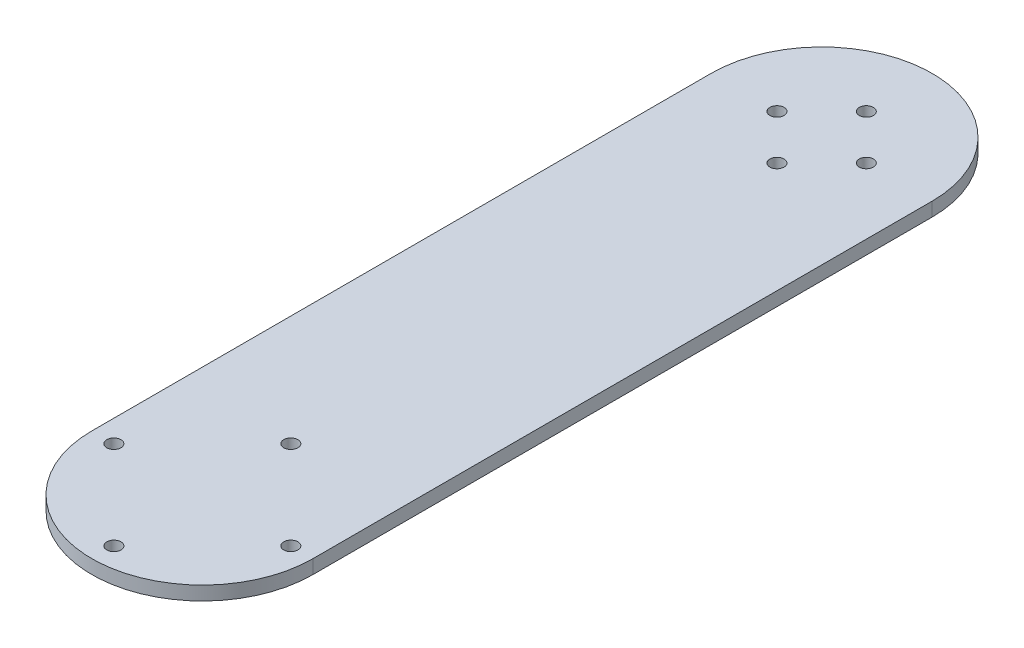
SolidWorks part; units mm, degrees
note: The reader was unsure of these and kept them because the rebuilt part matched: thickness of "Base-Flange1", "Sheet-Metal1", "Sheet-Metal2", "Sheet-Metal4".
ref_plane "Front Plane" through (0, 0, 0) normal (0, 0, 1) x (1, 0, 0)
ref_plane "Top Plane" through (0, 0, 0) normal (0, 1, 0) x (1, 0, 0)
ref_plane "Right Plane" through (0, 0, 0) normal (1, 0, 0) x (0, 0, -1)
sketch "Sketch1" plane through (0, 0, 0) normal (0, 1, 0) x (1, 0, 0)
  line L0 (0, 0) -> (0, -140) construction
  line L2 (-25, 0) -> (-25, -140)
  line L4 (25, 0) -> (25, -140)
  arc A0 (25, 0) -> (-25, 0) centre (0, 0) ccw
  arc A1 (-25, -140) -> (25, -140) centre (0, -140) ccw
  dimension "D1" = 25
  dimension "D5" = 25
  dimension "D2" = 140
  dimension "D3" = 50
base flange "Base-Flange1" sketch "Sketch1" thickness 3.125 reverse thickness direction no parameters "D1"=0.7366
sketch "Sketch4" plane through (0, -3.125, 0) normal (0, -1, 0) x (1, 0, 0)
  circle A0 centre (0, -10.0986) radius 1.6
  circle A1 centre (10.0986, 0) radius 1.6
  circle A2 centre (-10.0986, 0) radius 1.6
  circle A3 centre (0, 10.0986) radius 1.6
  dimension "D1" = 3.2
extrude "Cut-Extrude1" cut sketch "Sketch4" against normal through all normal cut yes
sketch "Sketch6" plane through (0, 0, 0) normal (0, 1, 0) x (1, 0, 0)
  circle A0 centre (-20, -140) radius 1.25 construction
  circle A1 centre (0, -160) radius 1.25 construction
  circle A2 centre (20, -140) radius 1.25 construction
  circle A3 centre (0, -120) radius 1.25 construction
  circle A4 centre (-20, -140) radius 1.25 construction
  circle A5 centre (0, -160) radius 1.25 construction
  circle A6 centre (20, -140) radius 1.25 construction
  circle A7 centre (0, -120) radius 1.25 construction
  circle A8 centre (0, -120) radius 1.6
  circle A9 centre (-20, -140) radius 1.6
  circle A10 centre (0, -160) radius 1.6
  circle A11 centre (20, -140) radius 1.6
  dimension "D1" = 3.2
extrude "Cut-Extrude3" cut sketch "Sketch6" against normal through all normal cut yes
sketch "Bend-Lines1" [suppressed] plane through (0, 0, 0) normal (0, 1, 0) x (1, 0, 0)
sketch "Bounding-Box1" [suppressed] plane through (0, 0, 0) normal (0, 1, 0) x (1, 0, 0)
sheet metal parameters "Sheet-Metal1" thickness 3.125 parameters "D1"=0.7366
flat pattern "Flat-Pattern1" [suppressed]
sketch "Bend-Lines2" plane through (0, 0, 0) normal (0, 1, 0) x (1, 0, 0)
sketch3d "Bounding-Box2" [suppressed]
  line L0 (-36.8904, 33.0015, 0) -> (-23.5725, -206.3502, 0) construction
  line L1 (33.0015, 36.8904, 0) -> (46.3194, -202.4614, 0) construction
  line L2 (-36.8904, 33.0015, 0) -> (33.0015, 36.8904, 0) construction
  line L3 (-23.5725, -206.3502, 0) -> (46.3194, -202.4614, 0) construction
sheet metal parameters "Sheet-Metal2" thickness 3.125 parameters "D1"=0.7366, "D7"=12.7
flat pattern "Flat-Pattern1"
sketch "Bend-Lines2" plane through (0, 0, 0) normal (0, 1, 0) x (1, 0, 0)
sketch3d "Bounding-Box2" [suppressed]
  line L0 (-37.2555, 32.5888, 0) -> (-23.2777, -176.611, 0) construction
  line L1 (32.5888, 37.2554, 0) -> (46.5666, -171.9444, 0) construction
  line L2 (-37.2555, 32.5888, 0) -> (32.5888, 37.2554, 0) construction
  line L3 (-23.2777, -176.611, 0) -> (46.5666, -171.9444, 0) construction
sheet metal parameters "Sheet-Metal4" thickness 3.125 parameters "D1"=0.7366, "D7"=12.7
flat pattern "Flat-Pattern1"
sketch "Bend-Lines2" plane through (0, 0, 0) normal (0, 1, 0) x (1, 0, 0)
sketch3d "Bounding-Box2" [suppressed]
  line L0 (-25, 25, 0) -> (-25, -165, 0) construction
  line L1 (25, 25, 0) -> (25, -165, 0) construction
  line L2 (-25, 25, 0) -> (25, 25, 0) construction
  line L3 (-25, -165, 0) -> (25, -165, 0) construction
